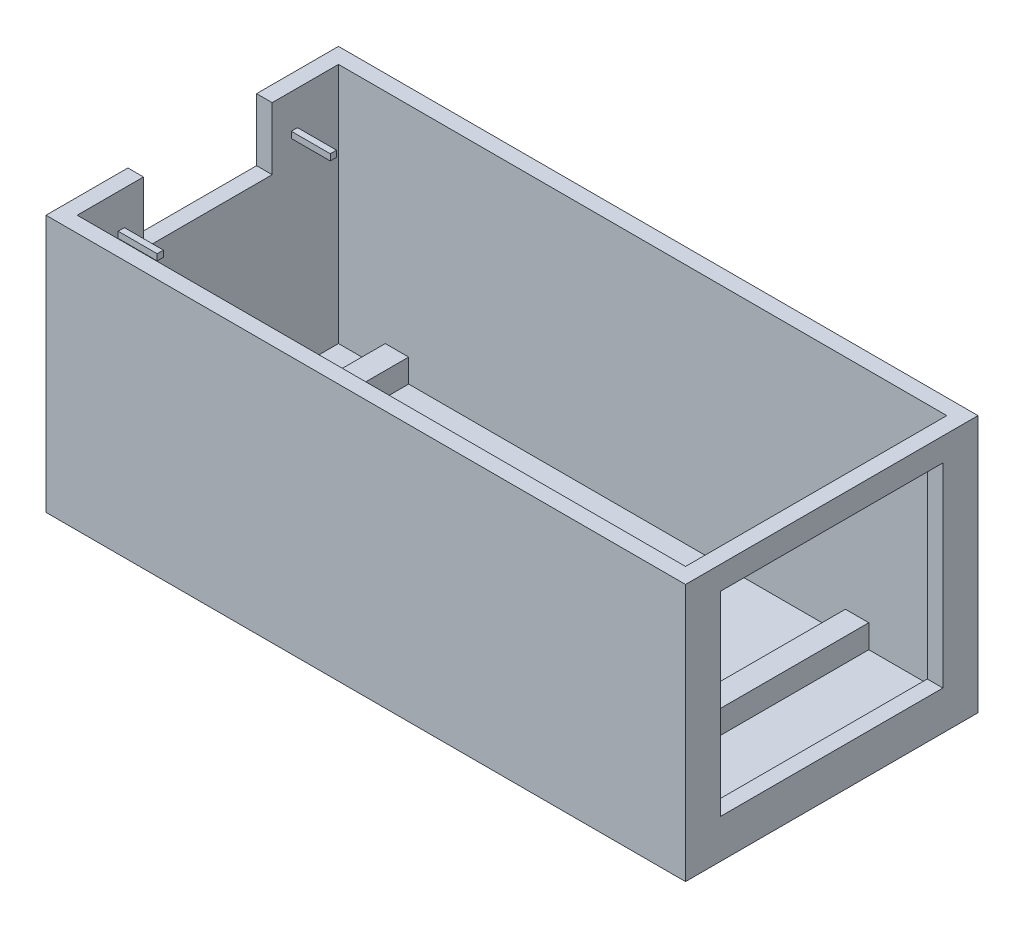
SolidWorks part; units mm, degrees
ref_plane "Front Plane" through (0, 0, 0) normal (0, 0, 1) x (1, 0, 0)
ref_plane "Top Plane" through (0, 0, 0) normal (0, 1, 0) x (1, 0, 0)
ref_plane "Right Plane" through (0, 0, 0) normal (1, 0, 0) x (0, 0, -1)
sketch "Sketch1" plane through (0, 0, 0) normal (0, 1, 0) x (1, 0, 0)
  line L1 (0, 0) -> (82, 0)
  line L2 (0, 0) -> (0, 37.5)
  line L3 (0, 37.5) -> (82, 37.5)
  line L4 (82, 0) -> (82, 37.5)
  dimension "D1" = 82
  dimension "D2" = 37.5
extrude "Boss-Extrude2" add sketch "Sketch1" along normal blind 2 contours L2 L3 L4 L1
sketch "Sketch2" plane through (0, 2, 0) normal (0, 1, 0) x (1, 0, 0)
  line L0 (0, 37.5) -> (82, 37.5) construction
  line L1 (8, 37.5) -> (11, 37.5)
  line L2 (8, 37.5) -> (8, 0)
  line L3 (8, 0) -> (11, 0)
  line L4 (11, 37.5) -> (11, 0)
  line L5 (0, 0) -> (82, 0) construction
  line L6 (0, 0) -> (0, 37.5) construction
  line L7 (67, 37.5) -> (70, 37.5)
  line L8 (67, 37.5) -> (67, 0)
  line L9 (67, 0) -> (70, 0)
  line L10 (70, 37.5) -> (70, 0)
  line L11 (82, 0) -> (82, 37.5) construction
  dimension "D1" = 3
  dimension "D2" = 8
  dimension "D3" = 12
  dimension "D4" = 3
extrude "Boss-Extrude4" add sketch "Sketch2" along normal blind 3
sketch "Sketch4" plane through (0, 2, 0) normal (0, 1, 0) x (1, 0, 0)
  line L0 (11, 37.5) -> (8, 37.5) construction
  line L1 (11, 37.5) -> (67, 37.5) construction
  line L2 (70, 37.5) -> (67, 37.5) construction
  line L3 (70, 37.5) -> (82, 37.5) construction
  line L4 (82, 0) -> (82, 37.5) construction
  line L5 (70, 0) -> (82, 0) construction
  line L6 (67, 0) -> (70, 0) construction
  line L7 (11, 0) -> (67, 0) construction
  line L8 (8, 0) -> (11, 0) construction
  line L9 (0, 0) -> (8, 0) construction
  line L10 (0, 0) -> (0, 37.5) construction
  line L11 (0, 37.5) -> (8, 37.5) construction
  line L12 (11, 37.5) -> (8, 37.5)
  line L13 (11, 37.5) -> (67, 37.5)
  line L14 (70, 37.5) -> (67, 37.5)
  line L15 (70, 37.5) -> (82, 37.5)
  line L16 (82, 0) -> (82, 37.5)
  line L17 (70, 0) -> (82, 0)
  line L18 (67, 0) -> (70, 0)
  line L19 (11, 0) -> (67, 0)
  line L20 (8, 0) -> (11, 0)
  line L21 (0, 0) -> (8, 0)
  line L22 (0, 0) -> (0, 37.5)
  line L23 (0, 37.5) -> (8, 37.5)
  line L24 (2, 2) -> (2, 35.5)
  line L25 (2, 35.5) -> (8, 35.5)
  line L26 (11, 35.5) -> (8, 35.5)
  line L27 (11, 35.5) -> (67, 35.5)
  line L28 (70, 35.5) -> (67, 35.5)
  line L29 (70, 35.5) -> (80, 35.5)
  line L30 (80, 2) -> (80, 35.5)
  line L31 (70, 2) -> (80, 2)
  line L32 (67, 2) -> (70, 2)
  line L33 (11, 2) -> (67, 2)
  line L34 (8, 2) -> (11, 2)
  line L35 (2, 2) -> (8, 2)
  dimension "D1" = 2
extrude "Boss-Extrude5" add sketch "Sketch4" along normal blind 31
sketch "Sketch6" plane through (0, 0, 0) normal (-1, 0, 0) x (0, 0, 1)
  line L0 (-37.5, 33) -> (0, 33) construction
  line L1 (-27, 33) -> (-10.5, 33)
  line L2 (-27, 33) -> (-27, 25)
  line L3 (-27, 25) -> (-10.5, 25)
  line L4 (-10.5, 33) -> (-10.5, 25)
  line L5 (-18.75, 0) -> (-18.75, 33.7611) construction
  line L6 (0, 0) -> (-37.5, 0) construction
  dimension "D1" = 16.5
  dimension "D2" = 8
extrude "Cut-Extrude1" cut sketch "Sketch6" against normal blind 2
sketch "Sketch7" plane through (82, 0, 0) normal (1, 0, 0) x (0, 0, -1)
  line L0 (0, 0) -> (37.5, 0) construction
  line L1 (4.5, 30) -> (33, 30)
  line L2 (4.5, 30) -> (4.5, 5)
  line L3 (4.5, 5) -> (33, 5)
  line L4 (33, 30) -> (33, 5)
  line L5 (18.75, 0) -> (18.75, 34.1605) construction
  dimension "D1" = 25
  dimension "D2" = 28.5
  dimension "D3" = 5
extrude "Cut-Extrude2" cut sketch "Sketch7" against normal blind 2
sketch "Sketch8" plane through (2, 0, 0) normal (1, 0, 0) x (0, 0, -1)
  line L0 (10.5, 33) -> (2, 33) construction
  line L1 (7.25, 28.6) -> (8.05, 28.6)
  line L2 (7.25, 28.6) -> (7.25, 27.8)
  line L3 (7.25, 27.8) -> (8.05, 27.8)
  line L4 (8.05, 28.6) -> (8.05, 27.8)
  line L5 (10.5, 25) -> (10.5, 33) construction
  line L6 (18.75, 25) -> (18.75, 37.7153) construction
  line L7 (27, 25) -> (10.5, 25) construction
  line L8 (30.25, 28.6) -> (30.25, 27.8)
  line L9 (30.25, 28.6) -> (29.45, 28.6)
  line L10 (29.45, 28.6) -> (29.45, 27.8)
  line L11 (30.25, 27.8) -> (29.45, 27.8)
  point P8 (7.25, 28.2)
  point P9 (8.05, 28.2)
  point P14 (7.65, 27.8)
  point P19 (29.85, 27.8)
  dimension "D1" = 4.4
  dimension "D2" = 2.45
  dimension "D3" = 0.8
  dimension "D4" = 0.8
extrude "Boss-Extrude6" add sketch "Sketch8" along normal blind 5
sketch "Sketch9" plane through (0, 0, -37.5) normal (0, 0, -1) x (-1, 0, 0)
  line L0 (-82, 33) -> (-82, 0) construction
  line L1 (-70, 27) -> (-35, 27)
  line L2 (-70, 27) -> (-70, 25)
  line L3 (-70, 25) -> (-35, 25)
  line L4 (-35, 27) -> (-35, 25)
  line L5 (-70, 6) -> (-35, 6)
  line L6 (-70, 6) -> (-70, 4)
  line L7 (-70, 4) -> (-35, 4)
  line L8 (-35, 6) -> (-35, 4)
  line L10 (-82, 33) -> (0, 33) construction
  point P8 (-35, 5)
  dimension "D1" = 2
  dimension "D2" = 2
  dimension "D3" = 35
  dimension "D4" = 35
  dimension "D5" = 12
  dimension "D6" = 12
  dimension "D7" = 19
  dimension "D8" = 6
extrude "Boss-Extrude7" add sketch "Sketch9" along normal blind 2.4
